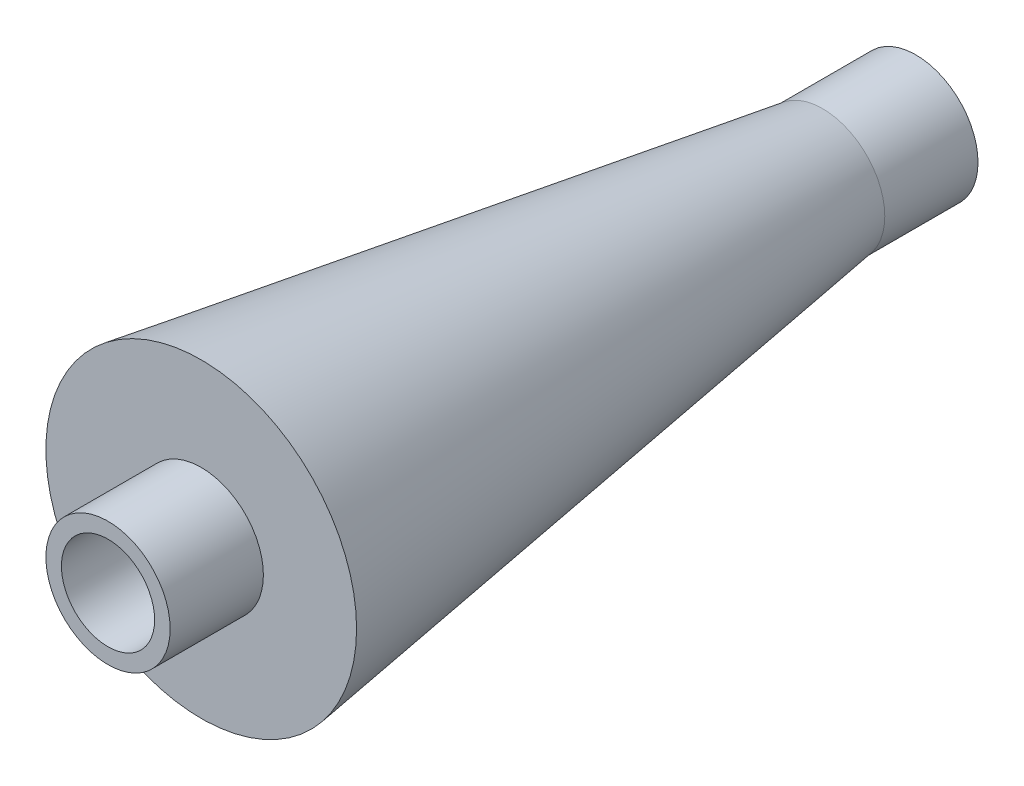
SolidWorks part; units mm, degrees
ref_plane "Front Plane" through (0, 0, 0) normal (0, 0, 1) x (1, 0, 0)
ref_plane "Top Plane" through (0, 0, 0) normal (0, 1, 0) x (1, 0, 0)
ref_plane "Right Plane" through (0, 0, 0) normal (1, 0, 0) x (0, 0, -1)
sketch "Sketch1" plane through (0, 0, 0) normal (0, 1, 0) x (1, 0, 0)
  line L0 (6.35, 19.05) -> (6.35, 9.525) construction
  line L1 (6.35, 9.525) -> (-6.35, 9.525) construction
  line L2 (15.875, 19.05) -> (-15.875, 19.05) construction
  line L3 (6.35, 92.075) -> (-6.35, 92.075) construction
  line L4 (6.35, 82.55) -> (6.35, 92.075) construction
  line L5 (6.35, 82.55) -> (15.875, 19.05) construction
  line L7 (6.35, 19.05) -> (6.35, 9.525)
  line L8 (6.35, 9.525) -> (4.7625, 9.525)
  line L9 (15.875, 19.05) -> (6.35, 19.05)
  line L10 (6.35, 92.075) -> (4.7625, 92.075)
  line L11 (6.35, 82.55) -> (6.35, 92.075)
  line L12 (6.35, 82.55) -> (15.875, 19.05)
  line L14 (4.7625, -1.5875) -> (4.7625, 104.775) construction
  line L15 (4.7625, 9.525) -> (4.7625, 92.075)
  line L16 (0, -1.5875) -> (0, 104.775) construction
  line L17 (0, -1.5875) -> (0, 104.775)
revolve "Revolve1" add sketch "Sketch1" angle 360 about L17 region at (8.3251, 0, -43.4163)
